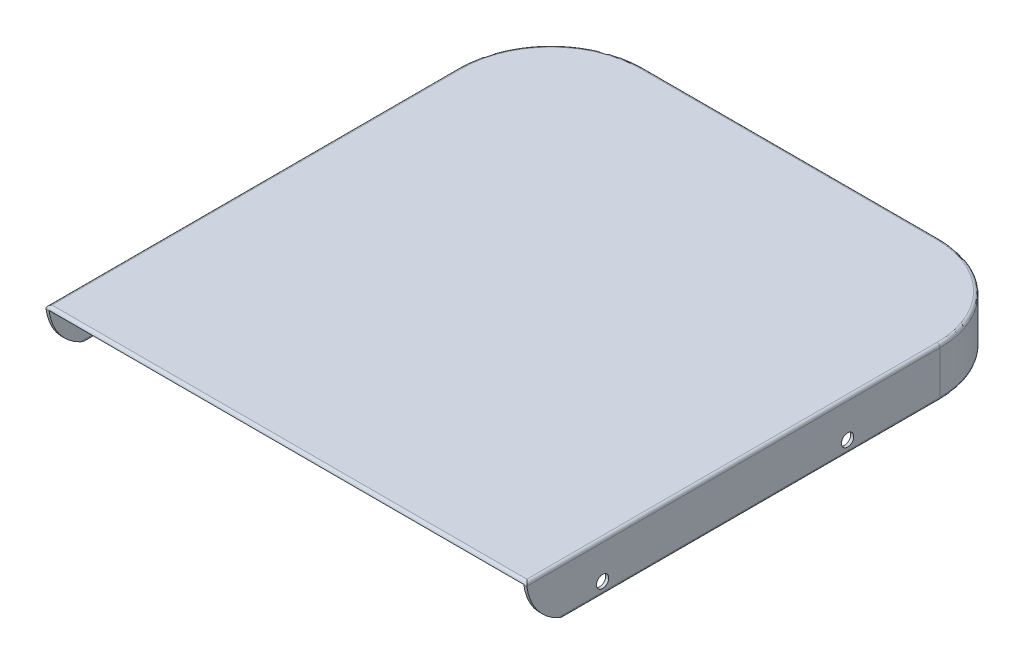
SolidWorks part; units mm, degrees
ref_plane "Front Plane" through (0, 0, 0) normal (0, 0, 1) x (1, 0, 0)
ref_plane "Top Plane" through (0, 0, 0) normal (0, 1, 0) x (1, 0, 0)
ref_plane "Right Plane" through (0, 0, 0) normal (1, 0, 0) x (0, 0, -1)
sketch "Sketch1" plane through (0, 0, 0) normal (0, 1, 0) x (1, 0, 0)
  line L1 (-48.5, 82.5) -> (48.5, 82.5)
  line L2 (-78.5, 52.5) -> (-78.5, -82.5)
  line L3 (-78.5, -82.5) -> (78.5, -82.5)
  line L4 (78.5, 52.5) -> (78.5, -82.5)
  line L5 (-78.5, 82.5) -> (78.5, -82.5) construction
  line L6 (-78.5, -82.5) -> (78.5, 82.5) construction
  arc A0 (48.5, 82.5) -> (78.5, 52.5) centre (48.5, 52.5) cw
  arc A1 (-48.5, 82.5) -> (-78.5, 52.5) centre (-48.5, 52.5) ccw
  point P0 (0, 0)
  dimension "D3" = 30
  dimension "D1" = 165
  dimension "D2" = 157
extrude "Boss-Extrude1" add sketch "Sketch1" along normal blind 16
sketch "Sketch2" plane through (0, 16, 0) normal (0, 1, 0) x (1, 0, 0)
  line L0 (78.5, -82.5) -> (78.5, 52.5) construction
  line L1 (-47.5, 81.5) -> (47.5, 81.5)
  line L2 (-77.5, 51.5) -> (-77.5, -81.5)
  line L4 (77.5, 51.5) -> (77.5, -81.5)
  line L5 (-77.5, 81.5) -> (77.5, -81.5) construction
  line L6 (-77.5, -81.5) -> (77.5, 81.5) construction
  line L8 (-77.5, -81.5) -> (-77.5, -82.5)
  line L9 (-78.5, -82.5) -> (78.5, -82.5) construction
  line L10 (-77.5, -82.5) -> (75.3928, -82.5)
  line L11 (77.5, -81.5) -> (77.5, -82.5)
  line L12 (77.5, -82.5) -> (75.3928, -82.5)
  line L13 (48.5, 82.5) -> (-48.5, 82.5) construction
  line L14 (-78.5, 52.5) -> (-78.5, -82.5) construction
  arc A0 (47.5, 81.5) -> (77.5, 51.5) centre (47.5, 51.5) cw
  arc A1 (-47.5, 81.5) -> (-77.5, 51.5) centre (-47.5, 51.5) ccw
  point P0 (0, 0)
  dimension "D3" = 30
  dimension "D4" = 1
  dimension "D1" = 1
  dimension "D2" = 1
extrude "Cut-Extrude1" cut sketch "Sketch2" against normal blind 25 from offset 1 offset against normal yes
sketch "Sketch5" plane through (-78.5, 0, 0) normal (-1, 0, 0) x (0, 0, 1)
  line L0 (-52.5, 0) -> (82.5, 0) construction
  line L1 (-52.5, 16) -> (82.5, 16) construction
  circle A0 centre (-22.3442, 4) radius 2
  circle A1 centre (57.6558, 4) radius 2
  dimension "D1" = 4
  dimension "D2" = 4
  dimension "D3" = 12
  dimension "D4" = 80
extrude "Cut-Extrude3" cut sketch "Sketch5" against normal through all
sketch "Sketch6" plane through (-78.5, 0, 0) normal (-1, 0, 0) x (0, 0, 1)
  line L0 (-52.5, 0) -> (82.5, 0) construction
  line L1 (69.5, 0) -> (82.5, 0)
  line L2 (82.5, 0) -> (82.5, 16)
  arc A0 (82.5, 16) -> (69.5, 0) centre (64.5608, 17.2943) cw
  line M4 (-52.5, 0) -> (82.5, 0)
  line M5 (82.5, 0) -> (82.5, 16)
  dimension "D1" = 13
extrude "Cut-Extrude4" cut sketch "Sketch6" against normal through all contours A0 M5 M4 region at (-78.5, 3.9017, 79.0613)
fillet "Fillet1" radius 1 16 edges at (77.5, 0, 9) (68.7132, 0, -72.7132) (0, 0, -81.5) (-68.7132, 0, -72.7132) (78.5, 0, 8.5) (69.7132, 0, -73.7132) (0, 0, -82.5) (-69.7132, 0, -73.7132) (-78.5, 16, 15) (-69.7132, 16, -73.7132) (0, 16, -82.5) (69.7132, 16, -73.7132) (78.5, 16, 15) (-77.5, 0, 9) (-78.5, 0, 8.5) (0, 16, 82.5)
